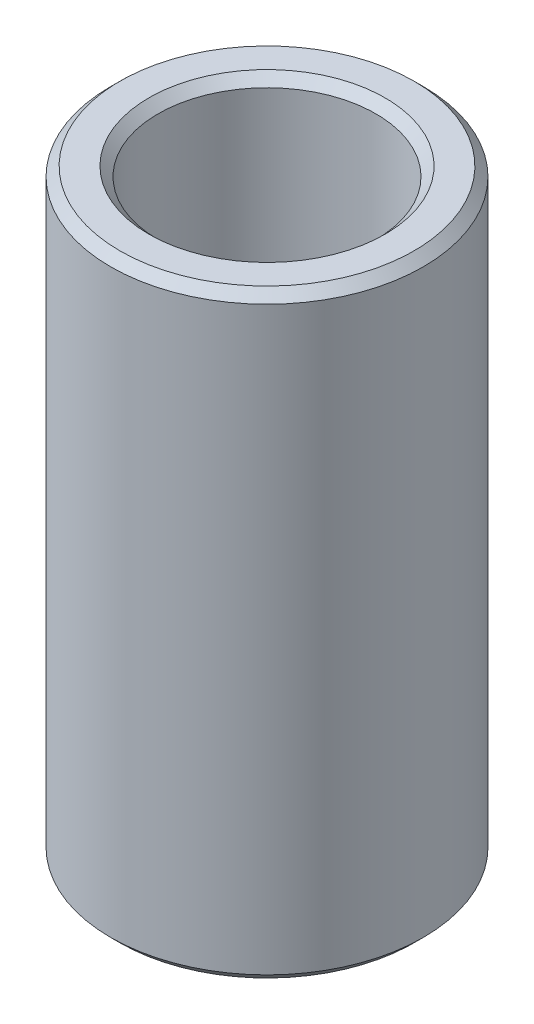
SolidWorks part; units mm, degrees
ref_plane "Front Plane" through (0, 0, 0) normal (0, 0, 1) x (1, 0, 0)
ref_plane "Top Plane" through (0, 0, 0) normal (0, 1, 0) x (1, 0, 0)
ref_plane "Right Plane" through (0, 0, 0) normal (1, 0, 0) x (0, 0, -1)
sketch "Sketch1" plane through (0, 0, 0) normal (0, 1, 0) x (1, 0, 0)
  circle A0 centre (0, 0) radius 37.5
  dimension "SLEEVE_OD" = 75
extrude "Boss-Extrude1" add sketch "Sketch1" along normal blind 143.821
sketch "Sketch2" plane through (0, 0, 0) normal (0, 1, 0) x (1, 0, 0)
  circle A0 centre (0, 0) radius 26.142
  dimension "BORE_D" = 52.284
extrude "Cut-Extrude1" cut sketch "Sketch2" along normal through all
chamfer "Chamfer1" distance 2.2126 angle 45 4 edges at (0, 143.821, 26.142) (0, 0, 26.142) (0, 0, 37.5) (0, 143.821, 37.5)
